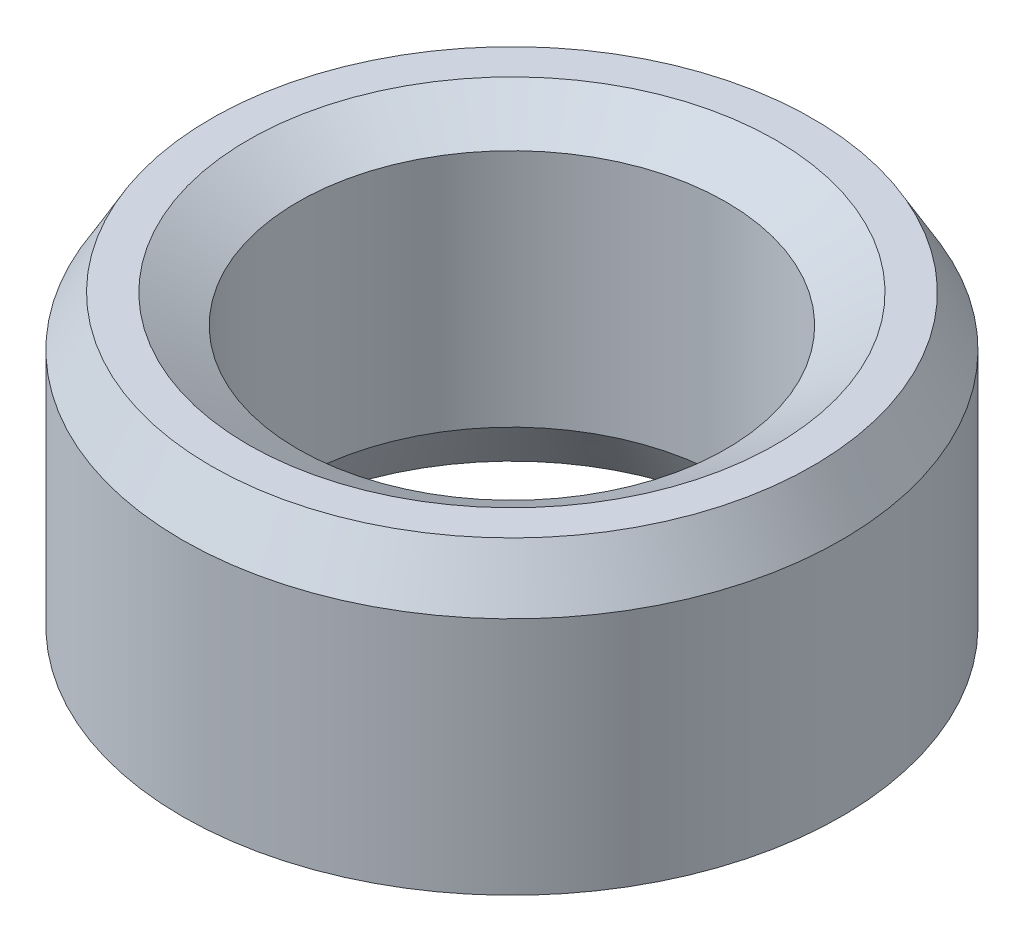
SolidWorks part; units mm, degrees
ref_plane "Front Plane" through (0, 0, 0) normal (0, 0, 1) x (1, 0, 0)
ref_plane "Top Plane" through (0, 0, 0) normal (0, 1, 0) x (1, 0, 0)
ref_plane "Right Plane" through (0, 0, 0) normal (1, 0, 0) x (0, 0, -1)
sketch "Sketch1" plane through (0, 0, 0) normal (0, 1, 0) x (1, 0, 0)
  circle A0 centre (0, 0) radius 7.5
  dimension "SLEEVE_OD" = 15
extrude "Boss-Extrude1" add sketch "Sketch1" along normal blind 7.2344
sketch "Sketch2" plane through (0, 0, 0) normal (0, 1, 0) x (1, 0, 0)
  circle A0 centre (0, 0) radius 4.8719
  dimension "BORE_D" = 9.7437
extrude "Cut-Extrude1" cut sketch "Sketch2" along normal through all
chamfer "Chamfer1" distance 1.1325 angle 30 4 edges at (0, 7.2344, 4.8719) (0, 0, 4.8719) (0, 0, 7.5) (0, 7.2344, 7.5) first distance on face at (0, 7.2344, 4.8719) first distance on face at (0, 0, 4.8719) first distance on face at (0, 7.2344, 7.5)
